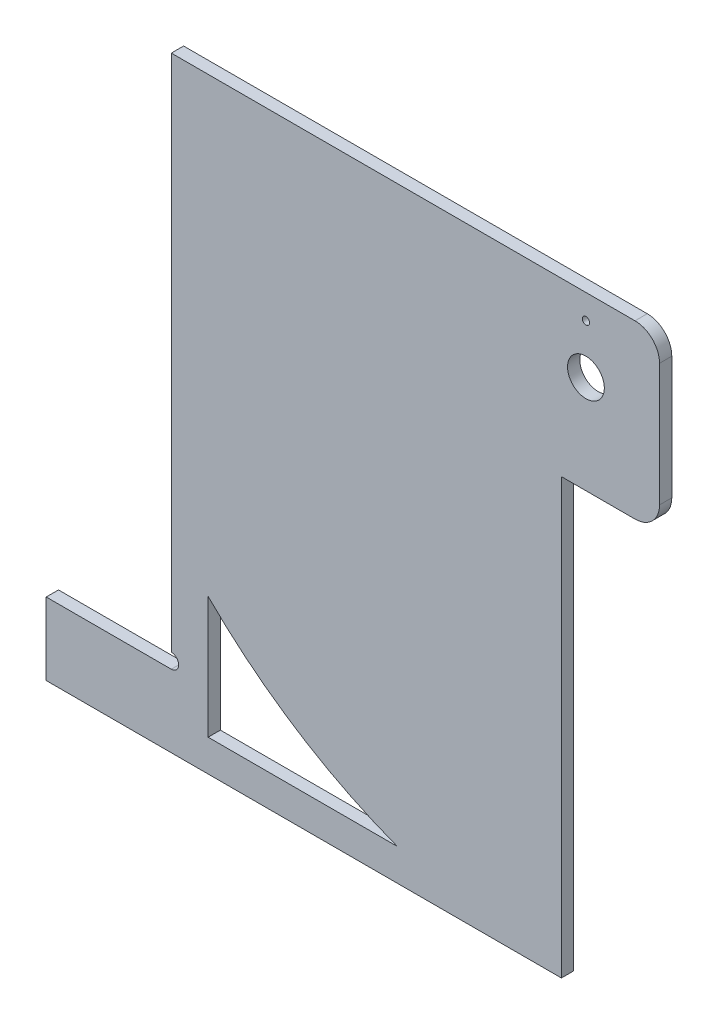
SolidWorks part; units mm, degrees
ref_plane "前视基准面" through (0, 0, 0) normal (0, 0, 1) x (1, 0, 0)
ref_plane "上视基准面" through (0, 0, 0) normal (0, 1, 0) x (1, 0, 0)
ref_plane "右视基准面" through (0, 0, 0) normal (1, 0, 0) x (0, 0, -1)
sketch "草图1" plane through (0, 0, 0) normal (0, 0, 1) x (1, 0, 0)
  line L0 (210, -237) -> (210, -247)
  line L1 (10, 0) -> (210, 0)
  line L2 (0, -10) -> (0, -237)
  line L3 (10, -247) -> (200, -247)
  line L4 (210, 0) -> (210, -237)
  line L5 (210, 0) -> (240, 0)
  line L6 (210, 0) -> (210, -70)
  line L7 (210, -70) -> (240, -70)
  line L8 (250, -10) -> (250, -60)
  line L9 (210, -247) -> (200, -247)
  line L10 (0, -237) -> (0, -247)
  line L11 (10, -247) -> (0, -247)
  arc A0 (240, 0) -> (250, -10) centre (240, -10) cw
  arc A1 (240, -70) -> (250, -60) centre (240, -60) ccw
  arc A4 (10, 0) -> (0, -10) centre (10, -10) ccw
  point P10 (250, 0)
  point P13 (250, -70)
  point P18 (0, -247)
  point P21 (0, 0)
  dimension "D5" = 10
  dimension "D1" = 247
  dimension "D2" = 210
  dimension "D3" = 40
  dimension "D4" = 70
extrude "凸台-拉伸1" add sketch "草图1" along normal blind 5 contours L3 L9 L0 L4 L1 A4 L2 L10 L11 | L6 L7 A1 L8 A0 L5
sketch "草图2" plane through (0, 0, 5) normal (0, 0, 1) x (1, 0, 0)
  line L0 (160.7676, 0) -> (160.7676, -30) construction
  line L1 (10, 0) -> (240, 0) construction
  line L2 (250, -30) -> (0, -30) construction
  line L3 (250, -10) -> (250, -60) construction
  line L4 (0, -10) -> (0, -247) construction
  line L5 (210, -70) -> (210, 0) construction
  line L6 (210, -30) -> (220, -30) construction
  circle A0 centre (220, -30) radius 7.5
  dimension "D3" = 15
  dimension "D1" = 30
  dimension "D2" = 10
extrude "切除-拉伸1" cut sketch "草图2" against normal blind 5
sketch "草图3" plane through (0, 0, 0) normal (-1, 0, 0) x (0, 0, 1)
  line L1 (0, -10) -> (0, -247) construction
  line L3 (5, -10) -> (5, -247) construction
  line L5 (5, -214.5) -> (6.3865, -214.5) construction
  line L16 (0, -217.5) -> (5, -217.5)
  line L19 (0, -217.5) -> (0, -211.5)
  line L20 (0, -211.5) -> (5, -211.5)
  line L21 (5, -217.5) -> (5, -211.5)
  point P15 (0, -214.5)
extrude "切除-拉伸3" cut sketch "草图3" against normal blind 51
sketch "草图4" plane through (0, 0, 5) normal (0, 0, 1) x (1, 0, 0)
  line L0 (51, -211.5) -> (51, -217.5) construction
  line L1 (51, -211.5) -> (51, -217.5)
  arc A0 (51, -217.5) -> (51, -211.5) centre (51, -214.5) ccw
extrude "切除-拉伸4" cut sketch "草图4" against normal up to next
sketch "草图7" plane through (0, 0, 5) normal (0, 0, 1) x (1, 0, 0)
  line L0 (10, 0) -> (240, 0) construction
  line L1 (0, -217.5) -> (51, -217.5)
  line L2 (0, -217.5) -> (0, 0)
  line L3 (0, 0) -> (51, 0)
  line L4 (51, -217.5) -> (51, 0)
extrude "切除-拉伸7" cut sketch "草图7" against normal up to next
sketch "草图8" plane through (0, 0, 0) normal (0, 0, -1) x (-1, 0, 0)
  line L0 (-62.701, -180.9338) -> (-66, -184.2984)
  line L1 (-66, -184.2984) -> (-66, -234)
  line L2 (-66, -234) -> (-143.1365, -234)
  line L3 (0, -247) -> (-210, -247) construction
  line L4 (-51, 0) -> (-51, -211.5) construction
  circle A0 centre (-220, -30) radius 215 construction
  circle A1 centre (-220, -30) radius 218
  dimension "D1" = 430
  dimension "D2" = 3
  dimension "D3" = 13
  dimension "D4" = 15
extrude "切除-拉伸9" cut sketch "草图8" against normal blind 10 contours A1 L2 L1 region at (89.5287, -218.6618, 0)
sketch "草图9" plane through (0, 0, 5) normal (0, 0, 1) x (1, 0, 0)
  line L0 (220.0008, 0) -> (220.0008, -10) construction
  line L1 (51, 0) -> (240, 0) construction
  line L2 (220, -30) -> (220.0008, 0) construction
  circle A0 centre (220.0008, -10) radius 1.5
  dimension "D2" = 3
  dimension "D1" = 10
extrude "切除-拉伸10" cut sketch "草图9" against normal up to surface (5 mm away) up to face at (227.5, -30, 0)
